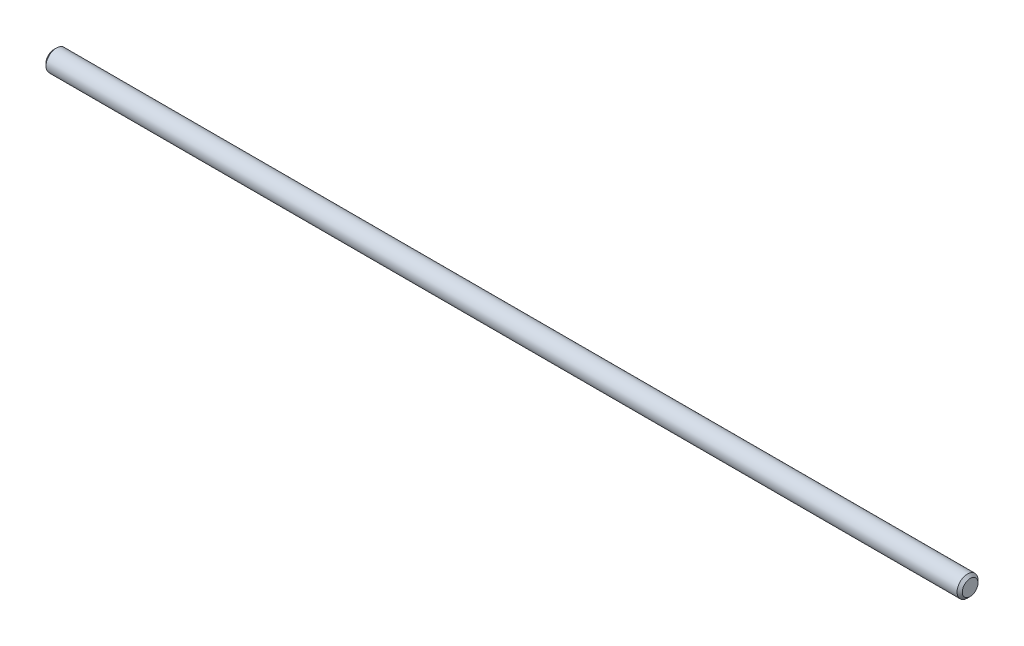
SolidWorks part; units mm, degrees
ref_plane "Alzado" through (0, 0, 0) normal (0, 0, 1) x (1, 0, 0)
ref_plane "Planta" through (0, 0, 0) normal (0, 1, 0) x (1, 0, 0)
ref_plane "Vista lateral" through (0, 0, 0) normal (1, 0, 0) x (0, 0, -1)
sketch "Croquis1" plane through (0, 0, 0) normal (1, 0, 0) x (0, 0, -1)
  circle A0 centre (0, 0) radius 4
  dimension "D1" = 8
extrude "Saliente-Extruir1" add sketch "Croquis1" along normal blind 175 and the other way blind 175
chamfer "Chaflán1" distance 1 angle 45 2 edges at (-175, 0, -4) (175, 0, -4)
